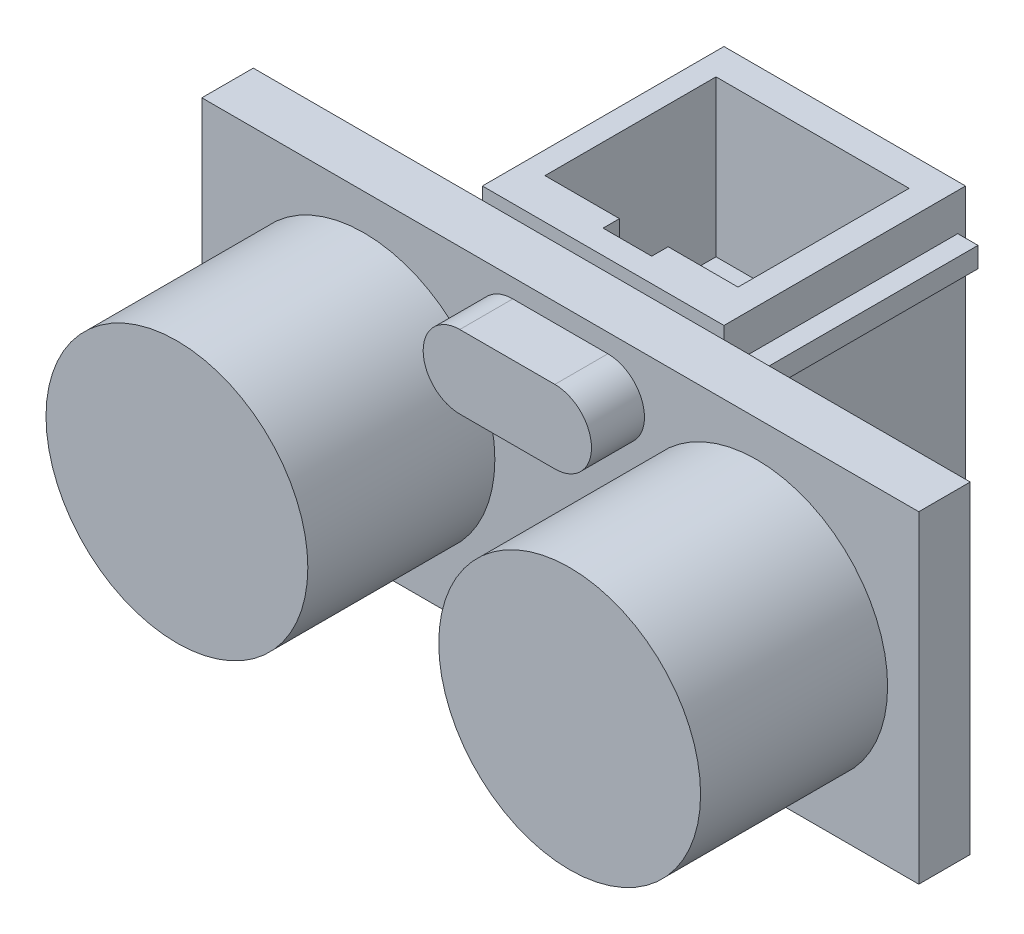
SolidWorks part; units mm, degrees
ref_plane "Front Plane" through (0, 0, 0) normal (0, 0, 1) x (1, 0, 0)
ref_plane "Top Plane" through (0, 0, 0) normal (0, 1, 0) x (1, 0, 0)
ref_plane "Right Plane" through (0, 0, 0) normal (1, 0, 0) x (0, 0, -1)
sketch "Sketch1" plane through (0, 0, 0) normal (0, 0, 1) x (1, 0, 0)
  line L1 (-23, -10.35) -> (23, -10.35)
  line L2 (-23, -10.35) -> (-23, 10.35)
  line L3 (-23, 10.35) -> (23, 10.35)
  line L4 (23, -10.35) -> (23, 10.35)
  line L5 (-23, -10.35) -> (23, 10.35) construction
  line L6 (-23, 10.35) -> (23, -10.35) construction
  point P0 (0, 0)
  dimension "D1" = 46
  dimension "D2" = 20.7
extrude "Boss-Extrude1" add sketch "Sketch1" along normal blind 3.3
sketch "Sketch2" plane through (0, 0, 3.3) normal (0, 0, 1) x (1, 0, 0)
  line L0 (-23, -0.35) -> (23, -0.35) construction
  line L1 (-23, 10.35) -> (-23, -10.35) construction
  line L2 (23, -10.35) -> (23, 10.35) construction
  line L3 (0, 0) -> (0, -0.35) construction
  line L4 (-12.6, -0.35) -> (0, 0) construction
  line L5 (0, 0) -> (12.6, -0.35) construction
  line L6 (23, 10.35) -> (-23, 10.35) construction
  circle A0 centre (-12.6, -0.35) radius 8.4
  circle A1 centre (12.6, -0.35) radius 8.4
  dimension "D1" = 25.2
  dimension "D2" = 16.8
  dimension "D3" = 10.7
extrude "Boss-Extrude2" add sketch "Sketch2" along normal blind 12
sketch "Sketch3" plane through (0, 0, 3.3) normal (0, 0, 1) x (1, 0, 0)
  line L0 (0, 0) -> (0, 13.591) construction
  line L1 (-3.05, 6.8) -> (3.05, 6.8) construction
  line L2 (-3.05, 9.15) -> (3.05, 9.15)
  line L3 (-3.05, 4.45) -> (3.05, 4.45)
  line L4 (23, 10.35) -> (-23, 10.35) construction
  arc A0 (-3.05, 9.15) -> (-3.05, 4.45) centre (-3.05, 6.8) ccw
  arc A1 (3.05, 4.45) -> (3.05, 9.15) centre (3.05, 6.8) ccw
  point P5 (0, 6.8)
  dimension "D3" = 10.8
  dimension "D1" = 1.2
  dimension "D2" = 4.7
extrude "Boss-Extrude3" add sketch "Sketch3" along normal blind 3.4
sketch "Sketch4" plane through (0, 0, 0) normal (0, 0, -1) x (-1, 0, 0)
  line L0 (23, -10.35) -> (-23, -10.35) construction
  line L1 (-7.2, 11.15) -> (8.3, 11.15)
  line L2 (-7.2, 11.15) -> (-7.2, -10.35)
  line L3 (-7.2, -10.35) -> (8.3, -10.35)
  line L4 (8.3, 11.15) -> (8.3, -10.35)
  line L5 (-23, 10.35) -> (23, 10.35) construction
  line L6 (-23, -10.35) -> (-23, 10.35) construction
  dimension "D1" = 0.8
  dimension "D2" = 15.5
  dimension "D3" = 15.8
extrude "Boss-Extrude4" add sketch "Sketch4" along normal blind 15.5
sketch "Sketch5" plane through (7.2, 0, 0) normal (1, 0, 0) x (0, 0, -1)
  line L0 (2.7, -10.35) -> (15.5, -6.45)
  line L1 (15.5, -10.35) -> (0, -10.35) construction
  line L2 (15.5, -6.45) -> (17.7624, -10.35)
  line L3 (17.7624, -10.35) -> (2.7, -10.35)
  line L4 (15.5, 11.15) -> (15.5, -10.35) construction
  dimension "D1" = 6
  dimension "D2" = 17.6
extrude "Cut-Extrude1" cut sketch "Sketch5" against normal through all
sketch "Sketch6" plane through (7.2, 0, 0) normal (1, 0, 0) x (0, 0, -1)
  line L0 (15.5, 11.15) -> (0, 11.15) construction
  line L1 (1, 8.75) -> (15, 8.75)
  line L2 (1, 8.75) -> (1, 7.45)
  line L3 (1, 7.45) -> (15, 7.45)
  line L4 (15, 8.75) -> (15, 7.45)
  line L5 (15.5, 11.15) -> (15.5, -6.45) construction
  line L6 (0, 10.35) -> (0, -10.35) construction
  dimension "D1" = 1.3
  dimension "D2" = 2.4
  dimension "D3" = 0.5
  dimension "D4" = 1
extrude "Boss-Extrude5" add sketch "Sketch6" along normal blind 1.3
sketch "Sketch7" plane through (-8.3, 0, 0) normal (-1, 0, 0) x (0, 0, 1)
  line L4 (-1, 8.75) -> (-15, 8.75)
  line L5 (-15, 8.75) -> (-15, 7.45)
  line L6 (-15, 7.45) -> (-1, 7.45)
  line L7 (-1, 7.45) -> (-1, 8.75)
  line L8 (-1, 8.75) -> (-15, 8.75)
  line L9 (-15, 8.75) -> (-15, 7.45)
  line L10 (-15, 7.45) -> (-1, 7.45)
  line L11 (-1, 7.45) -> (-1, 8.75)
  dimension "D1" = 0
extrude "Boss-Extrude6" add sketch "Sketch7" along normal blind 1.3
sketch "Sketch8" plane through (0, 11.15, 0) normal (0, 1, 0) x (1, 0, 0)
  line L0 (-0.55, 15.5) -> (-0.55, 0) construction
  line L1 (-8.3, 15.5) -> (7.2, 15.5) construction
  line L2 (7.2, 0) -> (-8.3, 0) construction
  line L4 (-6.8679, 2.5824) -> (5.5214, 2.5824)
  line L5 (-6.8679, 2.5824) -> (-6.8679, 13.5585)
  line L6 (-6.8679, 13.5585) -> (5.5214, 13.5585)
  line L7 (5.5214, 2.5824) -> (5.5214, 13.5585)
  line L8 (-2.086, 13.5585) -> (1.0353, 13.5585)
  line L9 (-2.086, 13.5585) -> (-2.086, 1.5297)
  line L10 (-2.086, 1.5297) -> (1.0353, 1.5297)
  line L11 (1.0353, 13.5585) -> (1.0353, 1.5297)
extrude "Cut-Extrude2" cut sketch "Sketch8" against normal blind 10 contours L9 L6 L5 L4 | L8 L0 L4 L11 | L0 L6 L9 L4 | L0 L4 L9 L10 | L4 L0 L10 L11 | L6 L11 L4 L7 region at (0.2426, 11.15, -8.0704) region at (-1.318, 11.15, -8.0704) region at (0.2426, 11.15, -2.056) region at (-1.318, 11.15, -2.056) region at (-4.4769, 11.15, -8.0704) region at (3.2783, 11.15, -8.0704)
